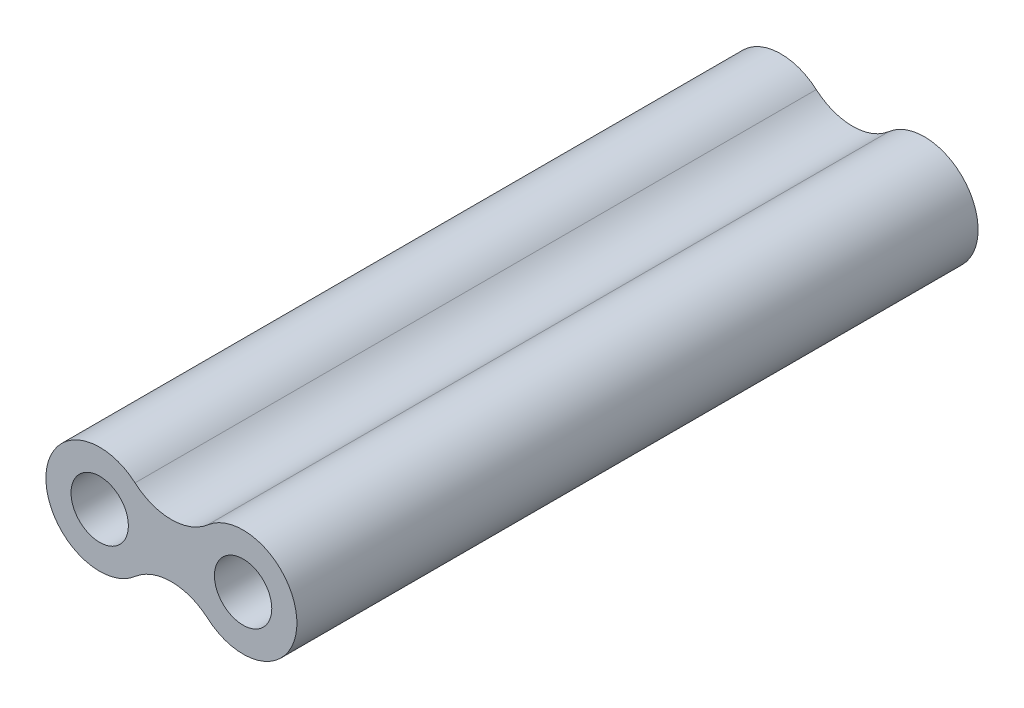
SolidWorks part; units mm, degrees
material "Rubber"
ref_plane "Front Plane" through (0, 0, 0) normal (0, 0, 1) x (1, 0, 0)
ref_plane "Top Plane" through (0, 0, 0) normal (0, 1, 0) x (1, 0, 0)
ref_plane "Right Plane" through (0, 0, 0) normal (1, 0, 0) x (0, 0, -1)
ref_axis "X" through (-88.99, 0, 0) along (1, 0, 0)
ref_axis "Y" through (0, 55, 0) along (0, -1, 0)
ref_axis "Z" through (0, 0, -88.99) along (0, 0, 1)
sketch "Sketch1" plane through (0, 0, 0) normal (0, 0, 1) x (1, 0, 0)
  circle A0 centre (0, 0) radius 1.5 construction
  circle A1 centre (0, 0) radius 3
  dimension "D1" = 3
  dimension "D2" = 6
extrude "Boss-Extrude1" add sketch "Sketch1" along normal mid plane 38
sketch "Sketch5" plane through (0, 0, 19) normal (0, 0, 1) x (1, 0, 0)
  point P0 (0, 0)
hole_wizard "M3 Clearance Hole1" positions "Sketch5" profile "Sketch4" hole size "M3" standard "ANSI Metric" end condition through all
sketch "Sketch4" plane through (0, 0, 19) normal (1, 0, 0) x (0, -1, 0)
  line L0 (0, 0) -> (0, 38)
  line L1 (0, 38) -> (1.6, 38)
  line L2 (1.6, 38) -> (1.6, 0)
  line L5 (1.6, 0) -> (0, 0)
  line L11 (0, -6.35) -> (0, 107.95) construction
  dimension "Thru Hole Dia." = 3.2
  dimension "Thru Hole Depth" = 38
sketch "Sketch2" plane through (0, 0, 0) normal (0, 0, 1) x (1, 0, 0)
  line L0 (0, 0) -> (8, 0) construction
  line L1 (4, 1.5) -> (4, -1.5) construction
  circle A0 centre (8, 0) radius 1.5 construction
  circle A1 centre (8, 0) radius 3
  circle A3 centre (0, 0) radius 3 construction
  circle A4 centre (0, 0) radius 1.5 construction
  arc A5 (1.9726, 2.2603) -> (6.0274, 2.2603) centre (4, 4.5833) ccw
  arc A6 (1.9726, -2.2603) -> (6.0274, -2.2603) centre (4, -4.5833) cw
  circle A7 centre (0, 0) radius 3
  dimension "D1" = 3
  dimension "D2" = 8
extrude "Boss-Extrude2" add sketch "Sketch2" along normal up to surface and the other way up to surface contours A1 | A7 A6 A1 A5 region at (8, 0, 0) region at (4, 0, 0) up to face at (1.6, 0, 19) other way up to face at (1.6, 0, -19)
sketch "Sketch8" plane through (0, 0, 19) normal (0, 0, 1) x (1, 0, 0)
  point P0 (8, 0)
hole_wizard "M3 Clearance Hole2" positions "Sketch8" profile "Sketch7" hole size "M3" standard "ANSI Metric" end condition through all
sketch "Sketch7" plane through (8, 0, 19) normal (1, 0, 0) x (0, -1, 0)
  line L0 (0, 0) -> (0, 38)
  line L1 (0, 38) -> (1.6, 38)
  line L2 (1.6, 38) -> (1.6, 0)
  line L5 (1.6, 0) -> (0, 0)
  line L11 (0, -6.35) -> (0, 107.95) construction
  dimension "Thru Hole Dia." = 3.2
  dimension "Thru Hole Depth" = 38
equation "\"Spacing\" = 8mm"
equation "\"D2@Sketch2\"=\"Spacing\""
